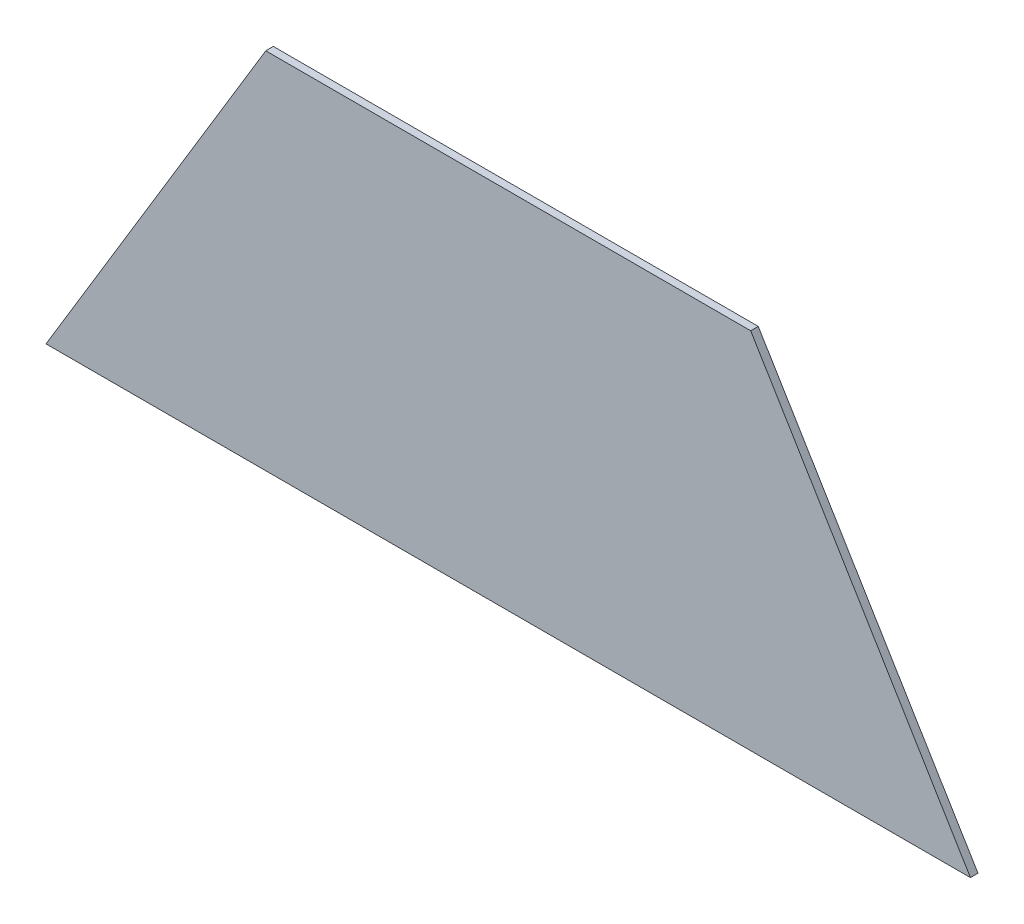
SolidWorks part; units mm, degrees
material "Printed Circuit Board"
ref_plane "Front Plane" through (0, 0, 0) normal (0, 0, 1) x (1, 0, 0)
ref_plane "Top Plane" through (0, 0, 0) normal (0, 1, 0) x (1, 0, 0)
ref_plane "Right Plane" through (0, 0, 0) normal (1, 0, 0) x (0, 0, -1)
sketch "Sketch1" plane through (0, 0, 0) normal (0, 0, 1) x (1, 0, 0)
  line L0 (0, 0) -> (193.675, 0)
  line L1 (193.675, 0) -> (101.6, 152.4)
  line L2 (101.6, 152.4) -> (0, 152.4)
  line L3 (0, 152.4) -> (-101.6, 152.4)
  line L4 (-101.6, 152.4) -> (-193.675, 0)
  line L5 (-193.675, 0) -> (0, 0)
  line L6 (0, 0) -> (0, 152.4) construction
  dimension "D1" = 152.4
  dimension "D2" = 387.35
  dimension "D3" = 203.2
extrude "Extrude1" add sketch "Sketch1" along normal mid plane 3.175
ref_plane "Plane1" through (0, 0, 0) normal (-1, 0, 0) x (0, 0, 1)
